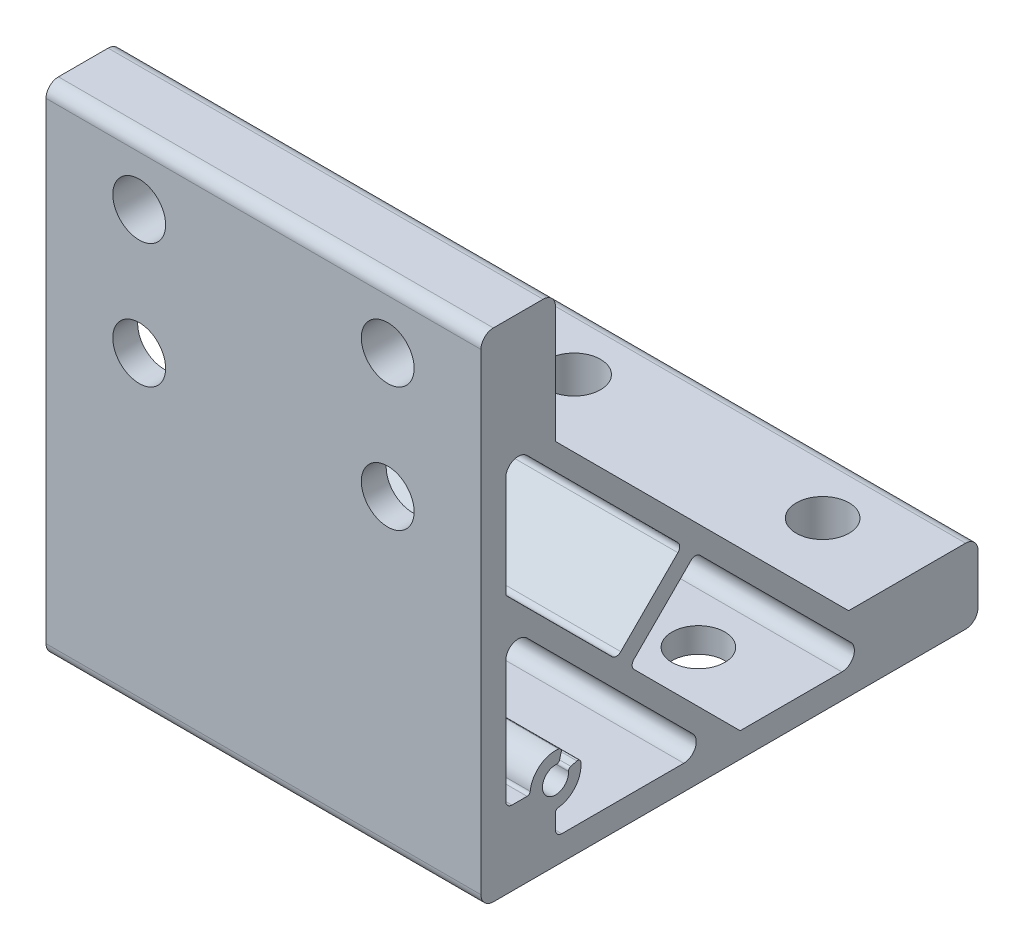
SolidWorks part; units mm, degrees
ref_plane "Front Plane" through (0, 0, 0) normal (0, 0, 1) x (1, 0, 0)
ref_plane "Top Plane" through (0, 0, 0) normal (0, 1, 0) x (1, 0, 0)
ref_plane "Right Plane" through (0, 0, 0) normal (1, 0, 0) x (0, 0, -1)
ref_axis "Axis_X" through (-11, 0, 0) along (1, 0, 0)
ref_axis "Axis_Y" through (0, 84, 0) along (0, -1, 0)
ref_axis "Axis_Z" through (0, 0, -84) along (0, 0, 1)
sketch "Sketch1" plane through (0, 0, 0) normal (1, 0, 0) x (0, 0, -1)
  line L0 (2, 0) -> (78, 0)
  line L1 (80, 2) -> (80, 10)
  line L2 (78, 12) -> (59.1769, 12)
  line L3 (59.1769, 12) -> (12, 59.1769)
  line L4 (12, 59.1769) -> (12, 78)
  line L5 (10, 80) -> (2, 80)
  line L6 (0, 78) -> (0, 2)
  line L7 (7.4142, 34.0642) -> (34.0642, 7.4142)
  line L8 (32.65, 4) -> (13, 4)
  line L9 (4, 13) -> (4, 32.65)
  line L10 (7.4273, 12) -> (5, 12)
  line L11 (12, 7.4273) -> (12, 5)
  line L12 (4, 58.1058) -> (4, 41.7211)
  line L13 (4, 41.7211) -> (21.0928, 24.6283)
  line L14 (22.507, 24.6283) -> (31.6994, 33.8207)
  line L15 (31.6994, 35.2349) -> (7.4142, 59.5201)
  line L16 (33.8207, 31.6994) -> (24.6283, 22.507)
  line L17 (24.6283, 21.0928) -> (41.7211, 4)
  line L18 (41.7211, 4) -> (58.1058, 4)
  line L19 (59.5201, 7.4142) -> (35.2349, 31.6994)
  line L20 (12.6604, 14.4645) -> (12.9227, 15.4436)
  line L21 (14.4645, 12.6604) -> (15.4436, 12.9227)
  line L22 (12, 12) -> (13.0612, 15.9603) construction
  line L23 (12, 12) -> (15.9603, 13.0612) construction
  arc A0 (12.1433, 14.0951) -> (14.0951, 12.1433) centre (12, 12) ccw
  arc A1 (12.4457, 7.9243) -> (16.0693, 12.5008) centre (12, 12) ccw
  arc A2 (12.5008, 16.0693) -> (7.9243, 12.4457) centre (12, 12) ccw
  arc A3 (0, 2) -> (2, 0) centre (2, 2) ccw
  arc A4 (12, 78) -> (10, 80) centre (10, 78) ccw
  arc A5 (0, 78) -> (2, 80) centre (2, 78) cw
  arc A6 (80, 10) -> (78, 12) centre (78, 10) ccw
  arc A7 (80, 2) -> (78, 0) centre (78, 2) cw
  arc A8 (7.9243, 12.4457) -> (7.4273, 12) centre (7.4273, 12.5) cw
  arc A9 (12, 7.4273) -> (12.4457, 7.9243) centre (12.5, 7.4273) cw
  arc A10 (12, 5) -> (13, 4) centre (13, 5) ccw
  arc A11 (4, 13) -> (5, 12) centre (5, 13) ccw
  arc A12 (7.4142, 34.0642) -> (4, 32.65) centre (6, 32.65) ccw
  arc A13 (34.0642, 7.4142) -> (32.65, 4) centre (32.65, 6) cw
  arc A14 (15.4436, 12.9227) -> (16.0693, 12.5008) centre (15.573, 12.4398) cw
  arc A15 (59.5201, 7.4142) -> (58.1058, 4) centre (58.1058, 6) cw
  arc A16 (14.4645, 12.6604) -> (14.0951, 12.1433) centre (14.5939, 12.1774) ccw
  arc A17 (4, 58.1058) -> (7.4142, 59.5201) centre (6, 58.1058) cw
  arc A18 (24.6283, 22.507) -> (24.6283, 21.0928) centre (25.3354, 21.7999) ccw
  arc A19 (35.2349, 31.6994) -> (33.8207, 31.6994) centre (34.5278, 30.9923) ccw
  arc A20 (31.6994, 33.8207) -> (31.6994, 35.2349) centre (30.9923, 34.5278) ccw
  arc A21 (21.0928, 24.6283) -> (22.507, 24.6283) centre (21.7999, 25.3354) ccw
  arc A22 (12.6604, 14.4645) -> (12.1433, 14.0951) centre (12.1774, 14.5939) cw
  arc A23 (12.5008, 16.0693) -> (12.9227, 15.4436) centre (12.4398, 15.573) cw
  point P29 (0, 0)
  point P32 (12, 80)
  point P35 (0, 80)
  point P38 (80, 12)
  point P51 (4, 37.4784)
  point P64 (23.9212, 21.7999)
  point P67 (34.5278, 32.4065)
  point P76 (59.1769, 12)
  dimension "FIX_3" = 4.2
  dimension "FIX_7" = 8.2
  dimension "FIX_17" = 2
  dimension "FIX_18" = 1
  dimension "FIX_19" = 0.5
  dimension "FIX_1" = 80
  dimension "FIX_2" = 12
  dimension "FIX_4" = 12
  dimension "FIX_5" = 12
  dimension "FIX_6" = 4
  dimension "FIX_8" = 45
  dimension "FIX_9" = 3
  dimension "FIX_10" = 3
  dimension "FIX_11" = 15
  dimension "FIX_12" = 15
  dimension "FIX_13" = 47.35
  dimension "FIX_14" = 3
  dimension "FIX_15" = 15
extrude "Boss-Extrude1" add sketch "Sketch1" along normal mid plane 70
cosmetic thread "Thread1" [suppressed] parameters "FIX_28"=20, "FIX_25"=5
cosmetic thread "Thread2" [suppressed] parameters "FIX_27"=20, "FIX_26"=5
hole_wizard "DiameterHole1" positions "Sketch3" profile "Sketch2" hole size "Ø6.5" standard "JIS" end condition up to next
sketch "Sketch3" plane through (0, 0, 0) normal (0, 0, 1) x (1, 0, 0)
  line L1 (-35, 78) -> (-35, 2) construction
  point P0 (-20, 70)
  point P2 (-20, 50)
  dimension "FIX_19" = 70
  dimension "FIX_20" = 50
  dimension "MSM_1" = 15
sketch "Sketch2" plane through (-20, 70, 0) normal (1, 0, 0) x (0, -1, 0)
  line L0 (0, 0) -> (0, 12)
  line L1 (0, 12) -> (4.25, 12)
  line L2 (4.25, 12) -> (4.25, 0)
  line L5 (4.25, 0) -> (0, 0)
  line L11 (0, -6.35) -> (0, 107.95) construction
  dimension "D" = 8.5
  dimension "HL_1" = 12
hole_wizard "DiameterHole2" positions "Sketch5" profile "Sketch4" hole size "Ø6.5" standard "JIS" end condition up to next
sketch "Sketch5" plane through (0, 0, 0) normal (0, -1, 0) x (-1, 0, 0)
  line L2 (35, 2) -> (35, 78) construction
  line L3 (-35, 0) -> (35, 0) construction
  point P6 (20, 70)
  point P8 (20, 50)
  dimension "FIX_22" = 50
  dimension "FIX_21" = 70
  dimension "MSM_1" = 15
sketch "Sketch4" plane through (-20, 0, -70) normal (1, 0, 0) x (0, 0, -1)
  line L0 (0, 0) -> (0, 12.001)
  line L1 (0, 12.001) -> (4.25, 12.001)
  line L2 (4.25, 12.001) -> (4.25, 0)
  line L5 (4.25, 0) -> (0, 0)
  line L11 (0, -6.35) -> (0, 107.95) construction
  dimension "D" = 8.5
  dimension "HL_1" = 12.001
sketch "Sketch6" plane through (0, 80, 0) normal (0, 1, 0) x (1, 0, 0)
  circle A0 centre (-20, 50) radius 7
  circle A2 centre (-20, 50) radius 4.25 construction
  dimension "D2_s" = 14
extrude "DiameterHole3" cut sketch "Sketch6" against normal up to next
sketch "Sketch7" plane through (0, 0, -80) normal (0, 0, -1) x (-1, 0, 0)
  circle A1 centre (20, 50) radius 4.25 construction
  circle A2 centre (20, 50) radius 7
  dimension "D2_s" = 14
extrude "DiameterHole4" cut sketch "Sketch7" against normal up to next
pattern_linear "LPattern1" count 2 spacing 40 along (1, 0, 0) of "DiameterHole1", "DiameterHole2", "DiameterHole4", "DiameterHole3"
pattern_linear "LPattern2" [suppressed] of bodies 104
equation "\"Factor\"= 1.082532"
